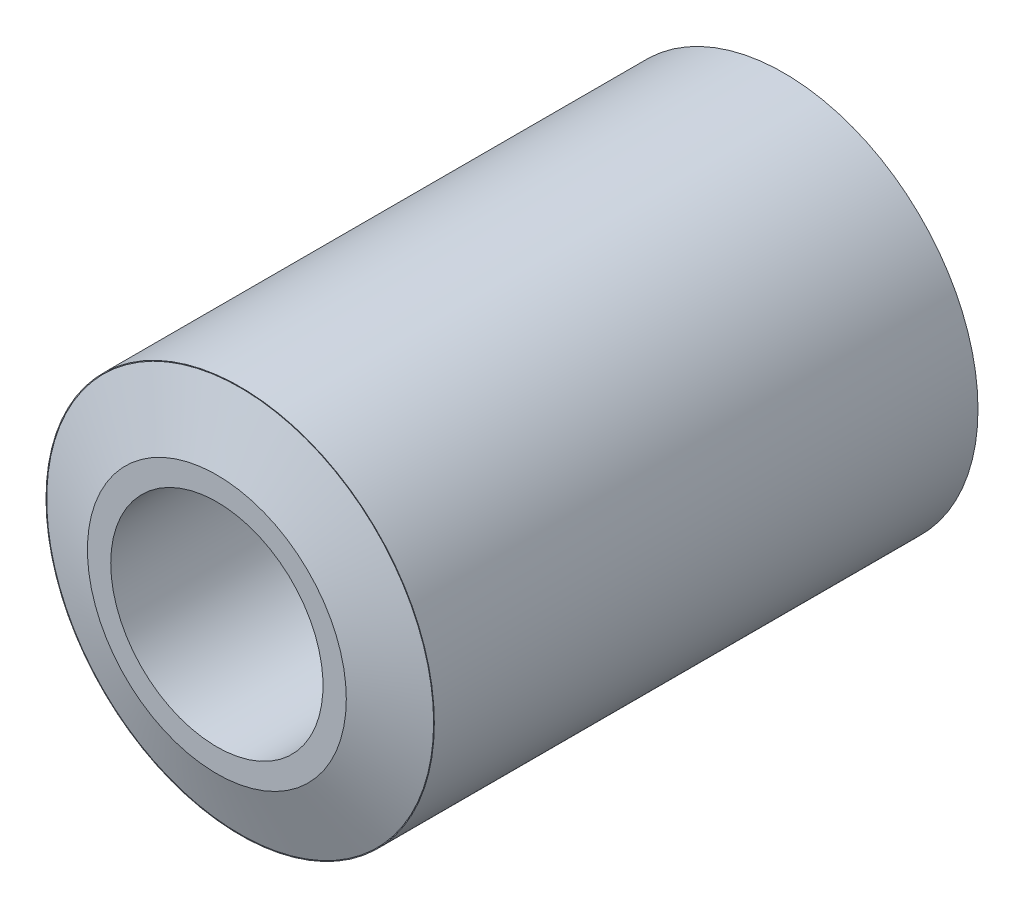
SolidWorks part; units mm, degrees
ref_plane "Front Plane" through (0, 0, 0) normal (0, 0, 1) x (1, 0, 0)
ref_plane "Top Plane" through (0, 0, 0) normal (0, 1, 0) x (1, 0, 0)
ref_plane "Right Plane" through (0, 0, 0) normal (1, 0, 0) x (0, 0, -1)
sketch "Sketch1" plane through (0, 0, 0) normal (0, 0, 1) x (1, 0, 0)
  circle A0 centre (0, 0) radius 7.5
  circle A1 centre (0, 0) radius 4.1
  dimension "D1" = 15
  dimension "D2" = 8.2
extrude "Boss-Extrude1" add sketch "Sketch1" along normal blind 21 contours A0 A1 region at (-7.2879, 0, 0)
sketch "Sketch2" plane through (0, 0, 0) normal (0, 0, 1) x (1, 0, 0)
  circle A0 centre (0, 0) radius 5
  circle A1 centre (0, 0) radius 4.1
  circle A2 centre (0, 0) radius 4.1 construction
  dimension "D1" = 10
extrude "Boss-Extrude2" add sketch "Sketch2" along normal offset from surface (22.8 mm away) 0.9 from offset 0.9 up to face at (4.1, 0, 21) offset beyond the face yes offset against normal yes
chamfer "Chamfer1" distance 0.9 angle 70 2 edges at (5, 0, 0) (5, 0, 21) first distance on face at (5, 0, -0.9) first distance on face at (5, 0, 21)
